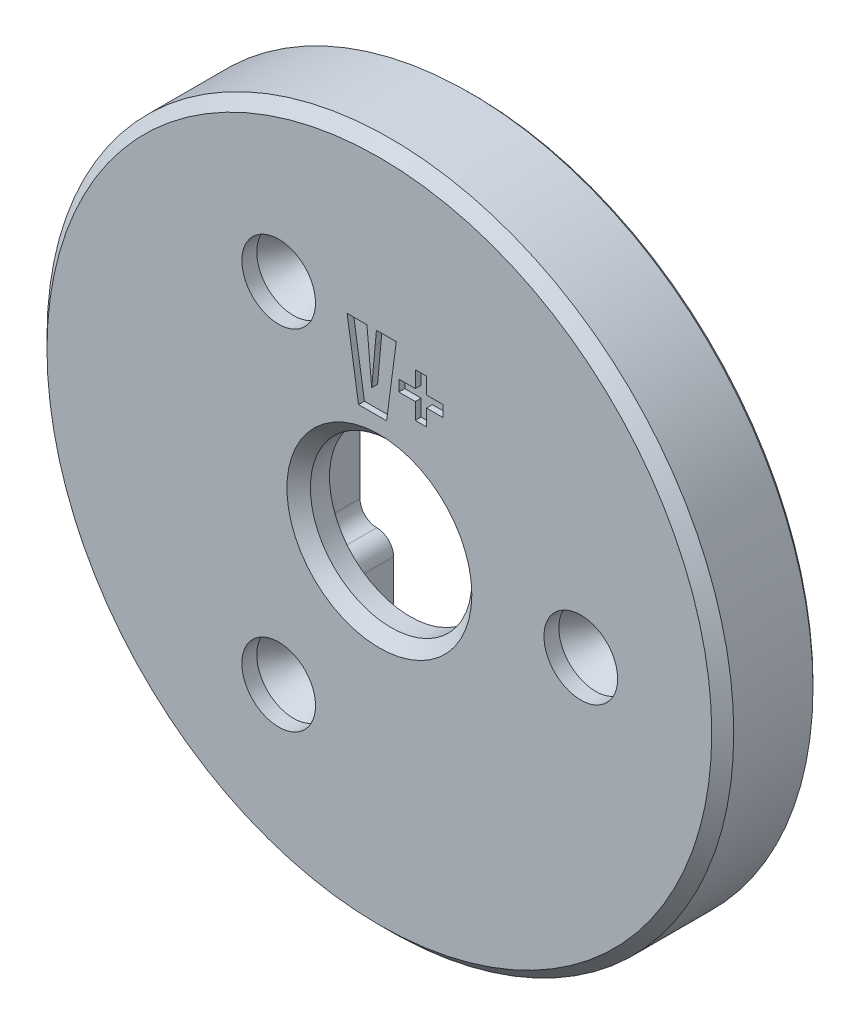
SolidWorks part; units mm, degrees
material "有机玻璃 (TM) GS 丙烯酸铸钣"
ref_plane "前视基准面" through (0, 0, 0) normal (0, 0, 1) x (1, 0, 0)
ref_plane "上视基准面" through (0, 0, 0) normal (0, 1, 0) x (1, 0, 0)
ref_plane "右视基准面" through (0, 0, 0) normal (1, 0, 0) x (0, 0, -1)
sketch "草图2" plane through (0, 0, 0) normal (0, 0, 1) x (1, 0, 0)
  circle A2 centre (100, 100) radius 21.6
sketch "草图3" plane through (0, 0, 0) normal (0, 0, 1) x (1, 0, 0)
  circle A0 centre (100, 100) radius 23.4
extrude "凸台-拉伸3" add sketch "草图3" along normal blind 6.4
extrude "切除-拉伸1" cut sketch "草图2" along normal blind 1.7
sketch "草图4" plane through (0, 0, 0) normal (0, 0, 1) x (1, 0, 0)
  line L0 (83.312, 98.171) -> (83.312, 101.854)
  line L1 (83.566, 97.917) -> (86.868, 97.917)
  line L2 (87.122, 98.171) -> (87.122, 101.727)
  line L3 (83.566, 102.108) -> (86.741, 102.108)
  line L4 (98.171, 114.173) -> (98.171, 115.57)
  line L5 (96.901, 114.173) -> (98.171, 114.173)
  line L6 (96.393, 106.045) -> (96.393, 113.665)
  line L7 (93.98, 97.155) -> (93.98, 103.632)
  line L8 (96.266, 83.693) -> (96.266, 94.869)
  line L9 (96.901, 83.058) -> (102.489, 83.058)
  line L10 (103.759, 84.328) -> (106.807, 84.328)
  line L11 (107.188, 84.709) -> (108.712, 84.709)
  line L12 (109.347, 85.344) -> (109.347, 86.868)
  line L13 (109.855, 87.376) -> (110.871, 87.376)
  line L14 (111.379, 87.884) -> (111.379, 88.646)
  line L15 (111.887, 89.154) -> (114.046, 89.154)
  line L16 (114.554, 89.662) -> (114.554, 91.059)
  line L17 (115.062, 91.567) -> (115.189, 91.567)
  line L18 (115.824, 92.202) -> (115.824, 94.615)
  line L19 (106.299, 94.869) -> (115.57, 94.869)
  line L20 (105.791, 95.377) -> (105.791, 102.616)
  line L21 (106.426, 103.251) -> (115.443, 103.251)
  line L22 (116.586, 102.108) -> (117.983, 102.108)
  line L23 (118.237, 102.362) -> (118.237, 102.997)
  line L24 (116.713, 104.521) -> (116.713, 109.093)
  line L25 (111.252, 109.855) -> (115.951, 109.855)
  line L26 (110.744, 110.363) -> (110.744, 113.411)
  line L27 (103.632, 114.427) -> (109.728, 114.427)
  line L28 (103.251, 114.808) -> (103.251, 115.57)
  line L29 (98.552, 115.951) -> (102.87, 115.951)
  arc A60 (83.566, 102.108) -> (83.312, 101.854) centre (83.566, 101.854) ccw
  arc A63 (83.312, 98.171) -> (83.566, 97.917) centre (83.566, 98.171) ccw
  arc A66 (86.868, 97.917) -> (87.122, 98.171) centre (86.868, 98.171) ccw
  arc A69 (87.122, 101.727) -> (86.741, 102.108) centre (86.741, 101.727) ccw
  arc A72 (98.552, 115.951) -> (98.171, 115.57) centre (98.552, 115.57) ccw
  arc A75 (96.901, 114.173) -> (96.393, 113.665) centre (96.901, 113.665) ccw
  arc A78 (95.25, 104.902) -> (96.393, 106.045) centre (95.25, 106.045) ccw
  arc A81 (95.25, 104.902) -> (93.98, 103.632) centre (95.25, 103.632) ccw
  arc A84 (93.98, 97.155) -> (95.123, 96.012) centre (95.123, 97.155) ccw
  arc A87 (96.266, 94.869) -> (95.123, 96.012) centre (95.123, 94.869) ccw
  arc A90 (96.266, 83.693) -> (96.901, 83.058) centre (96.901, 83.693) ccw
  arc A93 (102.489, 83.058) -> (102.87, 83.439) centre (102.489, 83.439) ccw
  arc A96 (103.759, 84.328) -> (102.87, 83.439) centre (103.759, 83.439) ccw
  arc A99 (106.807, 84.328) -> (106.934, 84.455) centre (106.807, 84.455) ccw
  arc A102 (107.188, 84.709) -> (106.934, 84.455) centre (107.188, 84.455) ccw
  arc A105 (108.712, 84.709) -> (109.347, 85.344) centre (108.712, 85.344) ccw
  arc A108 (109.855, 87.376) -> (109.347, 86.868) centre (109.855, 86.868) ccw
  arc A111 (110.871, 87.376) -> (111.379, 87.884) centre (110.871, 87.884) ccw
  arc A114 (111.887, 89.154) -> (111.379, 88.646) centre (111.887, 88.646) ccw
  arc A117 (114.046, 89.154) -> (114.554, 89.662) centre (114.046, 89.662) ccw
  arc A120 (115.062, 91.567) -> (114.554, 91.059) centre (115.062, 91.059) ccw
  arc A123 (115.189, 91.567) -> (115.824, 92.202) centre (115.189, 92.202) ccw
  arc A126 (115.824, 94.615) -> (115.57, 94.869) centre (115.57, 94.615) ccw
  arc A129 (105.791, 95.377) -> (106.299, 94.869) centre (106.299, 95.377) ccw
  arc A132 (106.426, 103.251) -> (105.791, 102.616) centre (106.426, 102.616) ccw
  arc A135 (116.078, 102.616) -> (115.443, 103.251) centre (115.443, 102.616) ccw
  arc A138 (116.078, 102.616) -> (116.586, 102.108) centre (116.586, 102.616) ccw
  arc A141 (117.983, 102.108) -> (118.237, 102.362) centre (117.983, 102.362) ccw
  arc A144 (118.237, 102.997) -> (117.729, 103.505) centre (117.729, 102.997) ccw
  arc A147 (116.713, 104.521) -> (117.729, 103.505) centre (117.729, 104.521) ccw
  arc A150 (116.713, 109.093) -> (115.951, 109.855) centre (115.951, 109.093) ccw
  arc A153 (110.744, 110.363) -> (111.252, 109.855) centre (111.252, 110.363) ccw
  arc A156 (110.744, 113.411) -> (109.728, 114.427) centre (109.728, 113.411) ccw
  arc A159 (103.251, 114.808) -> (103.632, 114.427) centre (103.632, 114.808) ccw
  arc A162 (103.251, 115.57) -> (102.87, 115.951) centre (102.87, 115.57) ccw
extrude "切除-拉伸2" cut sketch "草图4" along normal blind 2.6 from surface contours A162 L29 A72 L4 L5 A75 L6 A78 A81 L7 A84 A87 L8 A90 L9 A93 A96 L10 A99 A102 L11 A105 L12 A108 L13 region at (104.0257, 99.7178, 0) starting at face at (121.6, 100, 1.7)
sketch "草图5" plane through (0, 0, 0) normal (0, 0, 1) x (1, 0, 0)
  circle A0 centre (113.725, 100) radius 1.26
  circle A3 centre (93.1375, 88.1138) radius 1.26
  circle A6 centre (93.1375, 111.8862) radius 1.26
  circle A9 centre (100, 100) radius 5.5
extrude "切除-拉伸3" cut sketch "草图5" along normal up to surface (6.4 mm away) from surface contours A0 | A6 | A3 | A6 region at (113.725, 100, 0) region at (93.1375, 88.1138, 0) region at (93.1375, 111.8862, 0) up to face at (123.4, 100, 6.4) starting at face at (121.6, 100, 1.7)
extrude "切除-拉伸4" cut sketch "草图5<3>" along normal up to surface (6.4 mm away) from surface contours A9 region at (100, 100, 0) up to face at (114.985, 100, 6.4) starting at face at (107.6312, 98.717, 4.3)
sketch "草图5<3>" plane through (0, 0, 0) normal (0, 0, 1) x (1, 0, 0) same geometry as "草图5"
chamfer "倒角1" distance 0.75 angle 45 1 edges at (123.4, 100, 6.4)
sketch "草图6" plane through (0, 0, 0) normal (0, 0, 1) x (1, 0, 0)
  circle A0 centre (93.1375, 111.8862) radius 2.51
  circle A1 centre (93.1375, 88.1138) radius 2.51
  circle A2 centre (113.725, 100) radius 2.51
extrude "切除-拉伸5" cut sketch "草图6" against normal blind 1 from surface starting at face at (122.65, 100, 6.4)
chamfer "倒角2" distance 1.26 distance2 2 3 edges at (114.985, 100, 5.4) (94.3975, 88.1138, 5.4) (94.3975, 111.8862, 5.4) first distance on face at (114.985, 100, 5.4) first distance on face at (94.3975, 88.1138, 5.4) first distance on face at (94.3975, 111.8862, 5.4)
extrude "切除-拉伸6" cut sketch "草图4<3>" along normal blind 1.5 from surface contours L2 A69 L3 A60 L0 A63 L1 A66 region at (85.215, 100.0103, 0) starting at face at (114.985, 100, 1.7)
sketch "草图4<3>" plane through (0, 0, 0) normal (0, 0, 1) x (1, 0, 0) same geometry as "草图4"
chamfer "倒角3" distance 0.25 angle 45 2 edges at (123.4, 100, 0) (121.6, 100, 0)
chamfer "倒角4" distance 0.8 1 edges at (105.5, 100, 6.4)
sketch "草图7" plane through (0, 0, 0) normal (0, 0, 1) x (1, 0, 0)
  text T0 "V+" font "Impact" height 5
extrude "切除-拉伸7" cut sketch "草图7" against normal blind 0.4 from surface starting at face at (106.3, 100, 6.4)
